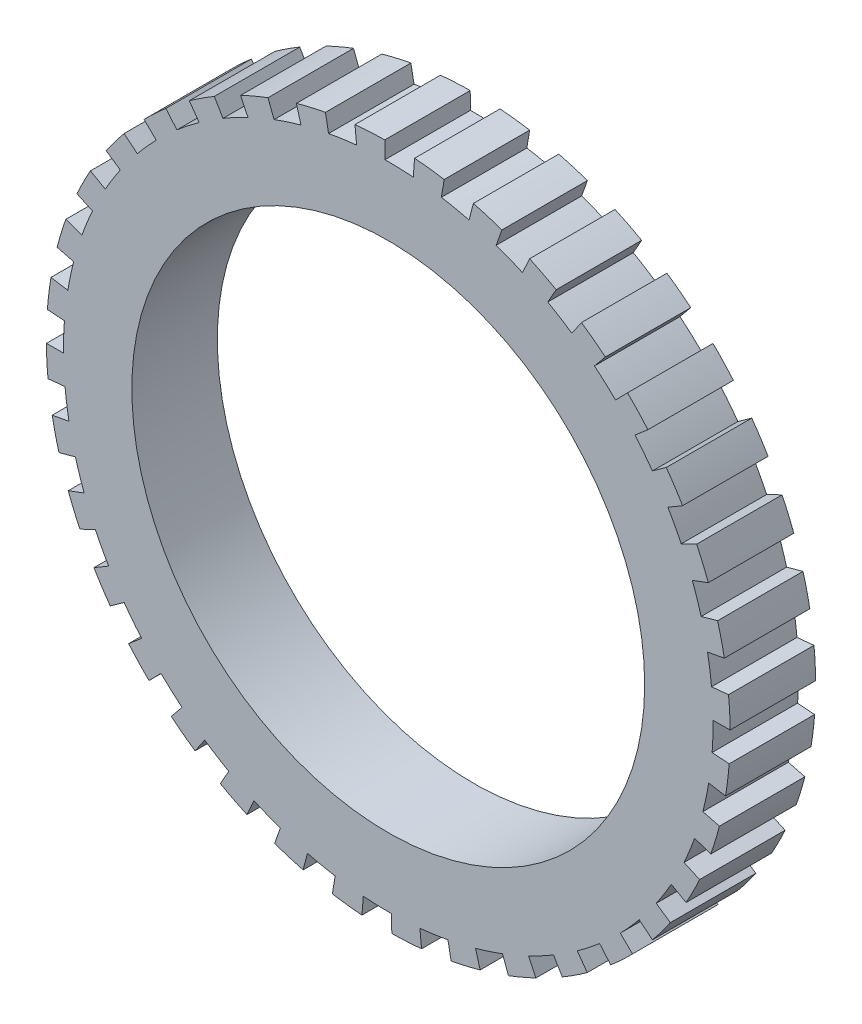
SolidWorks part; units mm, degrees
ref_plane "Front Plane" through (0, 0, 0) normal (0, 0, 1) x (1, 0, 0)
ref_plane "Top Plane" through (0, 0, 0) normal (0, 1, 0) x (1, 0, 0)
ref_plane "Right Plane" through (0, 0, 0) normal (1, 0, 0) x (0, 0, -1)
sketch "Sketch1" plane through (0, 0, 0) normal (0, 0, 1) x (1, 0, 0)
  circle A0 centre (0, 0) radius 15
  circle A1 centre (0, 0) radius 20
  dimension "D1" = 30
  dimension "D2" = 5
extrude "Boss-Extrude1" add sketch "Sketch1" along normal blind 5
sketch "Sketch2" plane through (0, 0, 5) normal (0, 0, 1) x (1, 0, 0)
  line L0 (-18.7443, 3.1067) -> (-19.7308, 3.2702)
  line L1 (-18.4022, 4.7286) -> (-19.3707, 4.9775)
  arc A0 (-18.4022, 4.7286) -> (-18.7443, 3.1067) centre (0, 0) ccw
  circle A1 centre (0, 0) radius 20 construction
  arc A2 (-19.3707, 4.9775) -> (-19.7308, 3.2702) centre (0, 0) ccw
  dimension "D1" = 1
  dimension "D2" = 5
extrude "Cut-Extrude1" cut sketch "Sketch2" against normal blind 5
sketch "Sketch3" plane through (0, 0, 5) normal (0, 0, 1) x (1, 0, 0)
  line L0 (0, -15) -> (0, 0)
  circle A0 centre (0, 0) radius 15 construction
ref_axis "Axis1" through (0, 0, 5) along (0, 0, 1)
pattern_circular "CirPattern1" count 36 over 360 about axis through (0, 0, 5) along (0, 0, 1) of "Cut-Extrude1"
scale "Scale1" scale about centroid uniform scaling yes scale factor 1.9329
scale "Scale2" scale about centroid uniform scaling yes scale factor 1.5
